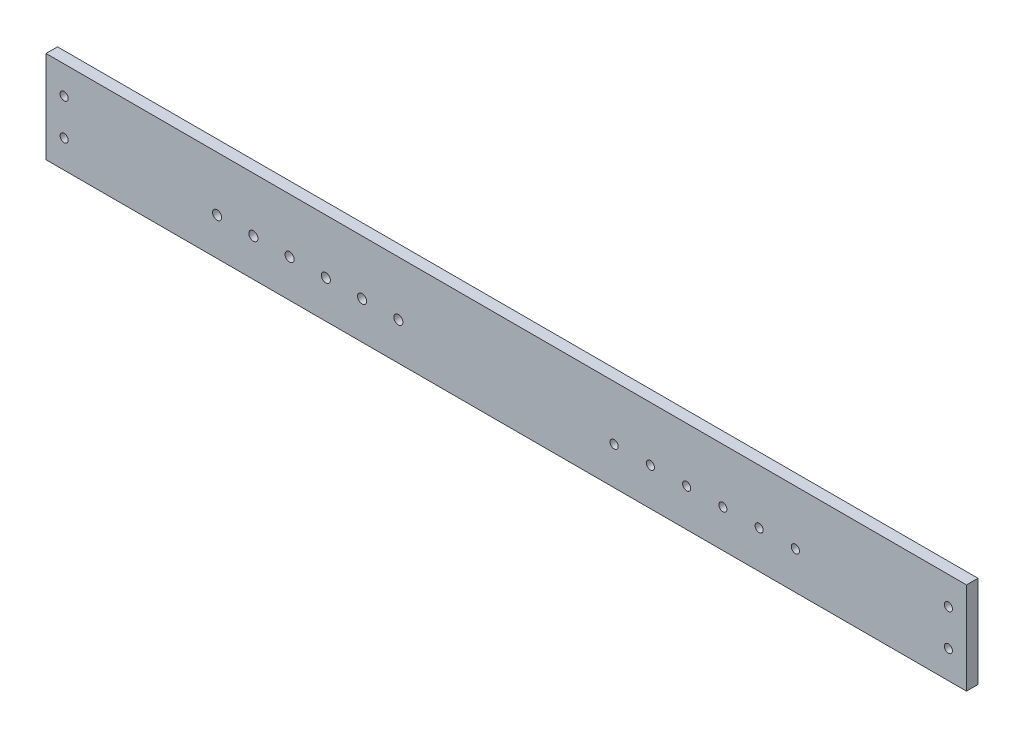
SolidWorks part; units mm, degrees
ref_plane "Front Plane" through (0, 0, 0) normal (0, 0, 1) x (1, 0, 0)
ref_plane "Top Plane" through (0, 0, 0) normal (0, 1, 0) x (1, 0, 0)
ref_plane "Right Plane" through (0, 0, 0) normal (1, 0, 0) x (0, 0, -1)
sketch "Sketch1" plane through (0, 0, 0) normal (0, 0, 1) x (1, 0, 0)
  line L0 (-144.5491, 66.7327) -> (-144.5491, 41.3327)
  line L1 (-144.5491, 66.7327) -> (109.4509, 66.7327)
  line L2 (-144.5491, 41.3327) -> (109.4509, 41.3327)
  line L3 (109.4509, 66.7327) -> (109.4509, 41.3327)
  circle A0 centre (-139.5491, 59.0327) radius 1.125
  circle A1 centre (-139.5491, 49.0327) radius 1.125
  circle A2 centre (104.4509, 59.0327) radius 1.125
  circle A3 centre (104.4509, 49.0327) radius 1.125
  circle A4 centre (12.2309, 51.7327) radius 1.125
  circle A8 centre (22.2309, 51.7327) radius 1.125
  circle A9 centre (32.2309, 51.7327) radius 1.125
  circle A10 centre (42.2309, 51.7327) radius 1.125
  circle A11 centre (52.2309, 51.7327) radius 1.125
  circle A12 centre (62.2309, 51.7327) radius 1.125
  circle A13 centre (-97.3291, 51.7327) radius 1.25
  circle A14 centre (-87.3291, 51.7327) radius 1.25
  circle A15 centre (-77.3291, 51.7327) radius 1.25
  circle A16 centre (-67.3291, 51.7327) radius 1.25
  circle A17 centre (-57.3291, 51.7327) radius 1.25
  circle A18 centre (-47.3291, 51.7327) radius 1.25
  dimension "D3" = 10
  dimension "D7" = 5
  dimension "D11" = 15
  dimension "D12" = 156.78
  dimension "D14" = 47.22
  dimension "D15" = 47.22
  dimension "D1" = 25.4
  dimension "D2" = 254
  dimension "D4" = 5
  dimension "D5" = 5
  dimension "D6" = 7.7
  dimension "D8" = 5
  dimension "D9" = 10
  dimension "D10" = 7.7
  dimension "D13" = 6
  dimension "D16" = 6
extrude "Boss-Extrude1" add sketch "Sketch1" along normal blind 3.175
